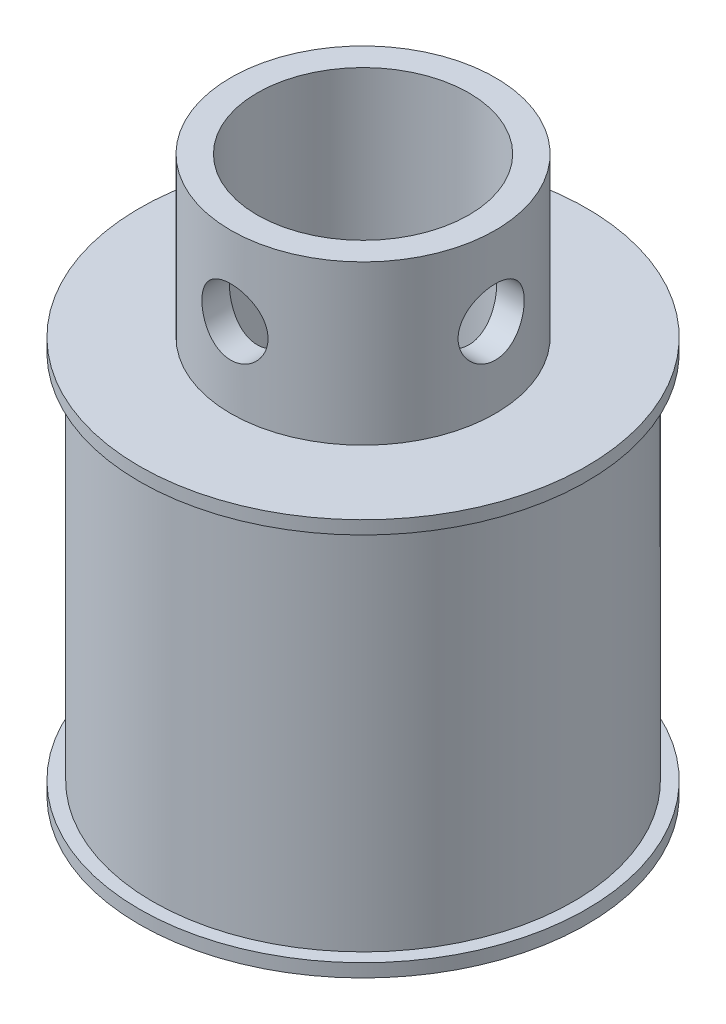
SolidWorks part; units mm, degrees
ref_plane "Alzado" through (0, 0, 0) normal (1, 0, 0) x (0, 1, 0)
ref_plane "Planta" through (0, 0, 0) normal (0, 0, 1) x (0, 1, 0)
ref_plane "Vista lateral" through (0, 0, 0) normal (0, 1, 0) x (-1, 0, 0)
sketch "Croquis1" plane through (0, 0, 0) normal (0, 1, 0) x (-1, 0, 0)
  circle A0 centre (0, 0) radius 7.95
  dimension "D1" = 15.9
extrude "Saliente-Extruir1" add sketch "Croquis1" along normal mid plane 15
sketch "Croquis2" plane through (0, 7.5, 0) normal (0, 1, 0) x (-1, 0, 0)
  circle A3 centre (0, 0) radius 8.45
  dimension "D1" = 16.9
extrude "Saliente-Extruir2" add sketch "Croquis2" against normal blind 0.5
extrude "Saliente-Extruir3" add sketch "Croquis2<2>" along normal blind 0.5 from surface starting at face at (0, -7.5, 7.95)
sketch "Croquis2<2>" plane through (0, 7.5, 0) normal (0, 1, 0) x (-1, 0, 0) same geometry as "Croquis2"
sketch "Croquis3" plane through (0, -7.5, 0) normal (0, 1, 0) x (-1, 0, 0)
  circle A0 centre (0, 0) radius 5
  dimension "D1" = 10
extrude "Saliente-Extruir4" add sketch "Croquis3" along normal blind 21
sketch "Croquis4" plane through (0, -7, 0) normal (0, 1, 0) x (-1, 0, 0)
  circle A0 centre (0, 0) radius 3
  dimension "D1" = 6
extrude "Cortar-Extruir1" cut sketch "Croquis4" against normal through all both and the other way through all
sketch "Croquis5" plane through (0, 0, 0) normal (0, 0, 1) x (0, 1, 0)
  line L4 (10.5, 5) -> (10.5, -5) construction
  line L5 (13.5, 5) -> (7.5, 5) construction
  line L9 (7.5, -5) -> (7.5, 5) construction
  line L10 (7.5, -5) -> (7.5, 5) construction
  point P10 (10.5, 0)
sketch "Croquis6" plane through (0, 0, 0) normal (1, 0, 0) x (0, 1, 0)
  point P0 (10.5, 0)
hole_wizard "Taladro roscado M32" positions "Croquis6" profile "Croquis7" tap size "M3" standard "DIN" end condition up to next
sketch "Croquis7" plane through (0, 10.5, 0) normal (0, 1, 0) x (0, 0, 1)
  line L0 (0, 0) -> (0, 5)
  line L1 (0, 5) -> (1.25, 5)
  line L2 (1.25, 5) -> (1.25, 0)
  line L5 (1.25, 0) -> (0, 0)
  line L11 (0, -6.35) -> (0, 107.95) construction
  dimension "Diámetro de perforador para roscar hasta el siguiente" = 2.5
  dimension "Profundidad de perforador para roscar hasta el siguiente" = 5
cosmetic thread "Rosca de taladro1" parameters "D2"=3
hole_wizard "Taladro roscado M31" positions "Croquis5" profile "Croquis9" tap size "M3" standard "DIN" end condition through all
sketch "Croquis9" plane through (0, 10.5, 0) normal (1, 0, 0) x (0, 1, 0)
  line L0 (0, 0) -> (0, 8.45)
  line L1 (0, 8.45) -> (1.25, 8.45)
  line L2 (1.25, 8.45) -> (1.25, 0)
  line L5 (1.25, 0) -> (0, 0)
  line L11 (0, -6.35) -> (0, 107.95) construction
  dimension "Diámetro de perforador para roscar hasta el siguiente" = 2.5
  dimension "Profundidad de perforador para roscar hasta el siguiente" = 8.45
cosmetic thread "Rosca de taladro2" parameters "D2"=3
ref_axis "Eje1" through (0, 10.5, 5) along (0, 0, -1)
ref_axis "Eje2" through (5, 10.5, 0) along (-1, 0, 0)
sketch "Croquis10" plane through (0, -7.5, 0) normal (0, -1, 0) x (1, 0, 0)
  circle A0 centre (0, 0) radius 4
  dimension "D1" = 8
extrude "Cortar-Extruir2" cut sketch "Croquis10" against normal through all
equation "\"Dp\"= 15.9"
equation "\"D1@Croquis1\"=\"Dp\""
equation "\"Dm\"= 10"
equation "\"De\"= \"Dp\" + 1"
equation "\"F\"= 15"
equation "\"L\"= 21"
equation "\"D1@Croquis2\"=\"De\""
equation "\"D1@Saliente-Extruir1\"=\"F\""
equation "\"D1@Saliente-Extruir4\"=\"L\""
equation "\"agujero\"= 6"
equation "\"D1@Croquis4\"=\"agujero\""
